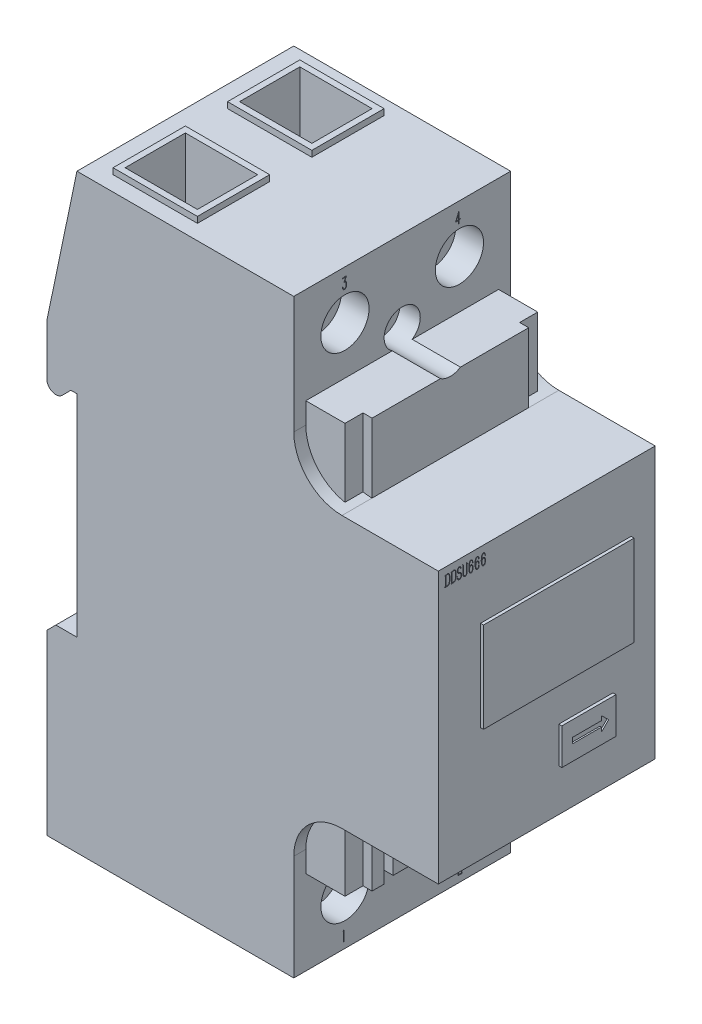
SolidWorks part; units mm, degrees
ref_plane "前视基准面" through (0, 0, 0) normal (0, 0, 1) x (1, 0, 0)
ref_plane "上视基准面" through (0, 0, 0) normal (0, 1, 0) x (1, 0, 0)
ref_plane "右视基准面" through (0, 0, 0) normal (1, 0, 0) x (0, 0, -1)
other "Configuration Table"
sketch "草图1" plane through (0, 0, 0) normal (0, 0, 1) x (1, 0, 0)
  line L0 (-48.1619, 0) -> (82.3002, 0) construction
  line L1 (0, 18) -> (0, -17)
  line L2 (0, -17) -> (-3.5, -17)
  line L3 (-5, -18.5) -> (-5, -48)
  line L4 (-5, -48) -> (36, -48)
  line L5 (36, -48) -> (36, -30.5)
  line L6 (44, -22.5) -> (60, -22.5)
  line L7 (60, -22.5) -> (60, 22.5)
  line L8 (60, 22.5) -> (44, 22.5)
  line L9 (36, 30.5) -> (36, 50)
  line L10 (36, 50) -> (0, 50)
  line L11 (0, 50) -> (-5, 26)
  line L12 (-5, 26) -> (-5, 17.6213)
  line L14 (0, 18) -> (-1, 18)
  line L15 (-1, 18) -> (-2.4393, 16.5607)
  line L16 (-3.5, -17) -> (-5, -18.5)
  arc A0 (36, -30.5) -> (44, -22.5) centre (44, -30.5) cw
  arc A1 (36, 30.5) -> (44, 22.5) centre (44, 30.5) ccw
  arc A2 (-5, 17.6213) -> (-2.4393, 16.5607) centre (-3.5, 17.6213) ccw
  point P5 (-5, -17)
  point P8 (60, 0)
  point P24 (-5, 14)
  dimension "D12" = 8
  dimension "D13" = 1.5
  dimension "D1" = 35
  dimension "D2" = 5
  dimension "D3" = 98
  dimension "D4" = 31
  dimension "D5" = 60
  dimension "D6" = 41
  dimension "D7" = 1
  dimension "D8" = 12
  dimension "D9" = 45
  dimension "D10" = 50
  dimension "D11" = 45
extrude "凸台-拉伸1" add sketch "草图1" along normal mid plane 36
sketch "草图3" plane through (0, 0, 0) normal (0, 1, 0) x (1, 0, 0)
  line L0 (36, -18) -> (36, 18) construction
  line L1 (36, -18) -> (36, 18) construction
  line L2 (24.7811, 0) -> (53.8019, 0) construction
  line L3 (36, 16) -> (36, -16)
  line L4 (36, -16) -> (42.5, -16)
  line L5 (42.5, -16) -> (42.5, -13)
  line L6 (42.5, -13) -> (44, -13)
  line L7 (44, -13) -> (44, 13)
  line L8 (44, 13) -> (42.5, 13)
  line L9 (42.5, 13) -> (42.5, 16)
  line L10 (42.5, 16) -> (36, 16)
  dimension "D1" = 6.5
  dimension "D2" = 8
  dimension "D3" = 32
  dimension "D4" = 26
extrude "凸台-拉伸4" add sketch "草图3" along normal mid plane 68
sketch "草图4" plane through (0, -22.5, 0) normal (0, -1, 0) x (1, 0, 0)
  line L0 (42.8853, 0) -> (54.8516, 0) construction
  line L2 (44, 13) -> (44, -13) construction
  line L4 (44, 13) -> (48, 13)
  line L5 (44, 13) -> (44, -13)
  line L6 (48, 13) -> (48, -13)
  line L7 (48, -13) -> (44, -13)
  dimension "D1" = 4
extrude "凸台-拉伸5" add sketch "草图4" along normal blind 4
sketch "草图5" plane through (0, -34, 0) normal (0, -1, 0) x (1, 0, 0)
  line L0 (48, -13) -> (48, 13) construction
  line L1 (48, -13) -> (48, 13)
  line L2 (28.9933, 0) -> (51.5375, 0) construction
  line L3 (36, 11) -> (36, -11)
  line L4 (36, -16) -> (36, 16) construction
  line L5 (36, -11) -> (46.5, -11)
  line L6 (46.5, -11) -> (46.5, 11)
  line L7 (46.5, 11) -> (36, 11)
  dimension "D1" = 1.5
  dimension "D2" = 22
extrude "切除-拉伸1" cut sketch "草图5" against normal blind 15 contours L3 L5 L6 L7
sketch "草图6" plane through (36, 0, 0) normal (1, 0, 0) x (0, 0, -1)
  line L0 (0, -48.641) -> (0, -19.05) construction
  line L1 (11, -26.5) -> (11, -34) construction
  line L2 (-10.5, -32.5) -> (10.5, -32.5)
  line L3 (-10.5, -32.5) -> (-10.5, -20.5)
  line L4 (-10.5, -20.5) -> (10.5, -20.5)
  line L5 (10.5, -32.5) -> (10.5, -20.5)
  line L6 (-10.5, -32.5) -> (10.5, -20.5) construction
  line L7 (-10.5, -20.5) -> (10.5, -32.5) construction
  line L8 (16, -34) -> (11, -34) construction
  point P3 (0, -26.5)
  dimension "D1" = 0.5
  dimension "D2" = 1.5
  dimension "D3" = 12
extrude "凸台-拉伸6" add sketch "草图6" along normal offset from surface (9 mm away) 1.5 up to face at (46.5, -22.75, 0)
hole_wizard "M2 开槽圆柱头螺钉的柱形沉头孔1" positions "草图15" profile "草图10" counterbore size "M2" standard "GB"
sketch "草图15" plane through (45, 0, 0) normal (1, 0, 0) x (0, 0, -1)
  line L0 (0, 4.0019) -> (0, -34.6889) construction
  line L3 (-10.5, -29.5) -> (10.5, -29.5) construction
  line L4 (-10.5, -20.5) -> (-10.5, -32.5) construction
  line L5 (10.5, -32.5) -> (10.5, -20.5) construction
  line L7 (13, -26.5) -> (-13, -26.5) construction
  point P0 (-7.5, -29.5)
  point P2 (-2.5, -29.5)
  point P4 (2.5, -29.5)
  point P6 (7.5, -29.5)
  dimension "D1" = 5
  dimension "D2" = 5
  dimension "D3" = 3
sketch "草图10" plane through (45, -29.5, 7.5) normal (0, 1, 0) x (0, 0, -1)
  line L0 (0, 0) -> (0, 4.721)
  line L1 (0, 4.721) -> (1.2, 4)
  line L2 (1.2, 4) -> (1.2, 2.3)
  line L3 (1.2, 2.3) -> (2.15, 2.3)
  line L4 (2.15, 2.3) -> (2.15, 0)
  line L5 (2.15, 0) -> (0, 0)
  line L10 (0, 4.721) -> (-1.2, 4) construction
  line L11 (0, -6.35) -> (0, 107.95) construction
  dimension "孔直径" = 2.4
  dimension "孔深度" = 4
  dimension "柱形沉头孔直径" = 4.3
  dimension "柱形沉头孔深度" = 2.3
  dimension "导头角度" = 118
sketch "草图16" plane through (0, -32.5, 0) normal (0, -1, 0) x (1, 0, 0)
  line L0 (40.5, 10.5) -> (40.5, -10.5) construction
  line L1 (45, 10.5) -> (36, 10.5) construction
  line L2 (45, -10.5) -> (36, -10.5) construction
  line L3 (36.8244, 0) -> (43.3826, 0) construction
  line L5 (42.25, 4.25) -> (38.75, 4.25)
  line L6 (42.25, 4.25) -> (42.25, 0.75)
  line L7 (42.25, 0.75) -> (38.75, 0.75)
  line L8 (38.75, 4.25) -> (38.75, 0.75)
  line L9 (42.25, 4.25) -> (38.75, 0.75) construction
  line L10 (42.25, 0.75) -> (38.75, 4.25) construction
  line L12 (38.75, -4.25) -> (38.75, -0.75)
  line L13 (42.25, -0.75) -> (38.75, -0.75)
  line L14 (42.25, -4.25) -> (42.25, -0.75)
  line L15 (42.25, -4.25) -> (38.75, -4.25)
  line L16 (38.75, -5.75) -> (42.25, -5.75)
  line L17 (38.75, 9.25) -> (42.25, 9.25)
  line L18 (38.75, 9.25) -> (38.75, 5.75)
  line L19 (38.75, 5.75) -> (42.25, 5.75)
  line L20 (42.25, 9.25) -> (42.25, 5.75)
  line L21 (38.75, 9.25) -> (42.25, 5.75) construction
  line L22 (38.75, 5.75) -> (42.25, 9.25) construction
  line L23 (38.75, -9.25) -> (38.75, -5.75)
  line L24 (38.75, -9.25) -> (42.25, -9.25)
  line L25 (42.25, -9.25) -> (42.25, -5.75)
  point P9 (40.5, 2.5)
  point P19 (38.75, 2.5)
  point P20 (38.75, -2.5)
  point P21 (40.5, 7.5)
  point P29 (38.75, 7.5)
  dimension "D1" = 3.5
  dimension "D2" = 5
  dimension "D3" = 5
extrude "切除-拉伸2" cut sketch "草图16" against normal blind 2
hole_wizard "M4 开槽圆柱头螺钉的柱形沉头孔1" positions "草图20" profile "草图19" counterbore size "M4" standard "GB"
sketch "草图20" plane through (36, 0, 0) normal (1, 0, 0) x (0, 0, -1)
  line L0 (-16.3132, 42) -> (15.3429, 42) construction
  line L2 (-18, 50) -> (18, 50) construction
  line L3 (0, 35.6579) -> (0, 47.3622) construction
  line L4 (-22.9234, 0) -> (24.0756, 0) construction
  line L6 (-16.3132, -40) -> (15.3429, -40) construction
  line L8 (0, -45.3622) -> (0, -34.8102) construction
  line L10 (-18, -48) -> (18, -48) construction
  point P0 (-9.5, 42)
  point P2 (9.5, 42)
  point P19 (-9.5, -40)
  point P21 (9.5, -40)
  dimension "D1" = 8
  dimension "D2" = 19
  dimension "D3" = 8
sketch "草图19" plane through (36, 42, 9.5) normal (0, 1, 0) x (0, 0, -1)
  line L0 (0, 0) -> (0, 6.3519)
  line L1 (0, 6.3519) -> (2.25, 5)
  line L2 (2.25, 5) -> (2.25, 4.6)
  line L3 (2.25, 4.6) -> (4, 4.6)
  line L4 (4, 4.6) -> (4, 0)
  line L5 (4, 0) -> (0, 0)
  line L10 (0, 6.3519) -> (-2.25, 5) construction
  line L11 (0, -6.35) -> (0, 107.95) construction
  dimension "孔直径" = 4.5
  dimension "孔深度" = 5
  dimension "柱形沉头孔直径" = 8
  dimension "柱形沉头孔深度" = 4.6
  dimension "导头角度" = 118
hole_wizard "M3 开槽圆柱头螺钉的柱形沉头孔1" positions "草图21" profile "草图22" counterbore size "M3" standard "GB"
sketch "草图21" plane through (36, 0, 0) normal (1, 0, 0) x (0, 0, -1)
  line L0 (-10.5, -32.5) -> (10.5, -32.5) construction
  line L1 (16, 34) -> (-16, 34) construction
  point P0 (0, 36.5)
  point P2 (0, -36.5)
  dimension "D1" = 4
  dimension "D2" = 2.5
sketch "草图22" plane through (36, 36.5, 0) normal (0, 1, 0) x (0, 0, -1)
  line L0 (0, 0) -> (0, 6.0215)
  line L1 (0, 6.0215) -> (1.7, 5)
  line L2 (1.7, 5) -> (1.7, 3.4)
  line L3 (1.7, 3.4) -> (3, 3.4)
  line L4 (3, 3.4) -> (3, 0)
  line L5 (3, 0) -> (0, 0)
  line L10 (0, 6.0215) -> (-1.7, 5) construction
  line L11 (0, -6.35) -> (0, 107.95) construction
  dimension "孔直径" = 3.4
  dimension "孔深度" = 5
  dimension "柱形沉头孔直径" = 6
  dimension "柱形沉头孔深度" = 3.4
  dimension "导头角度" = 118
sketch "草图23" plane through (44, 0, 0) normal (1, 0, 0) x (0, 0, -1)
  arc A0 (1.6583, 34) -> (-1.6583, 34) centre (0, 36.5) ccw construction
  arc A1 (1.6583, 34) -> (-1.6583, 34) centre (0, 36.5) ccw
  circle A2 centre (0, 36.5) radius 3
extrude "切除-拉伸3" cut sketch "草图23" against normal up to surface (8 mm away) contours A2 up to face at (36, 42, 5.5)
sketch "草图24" plane through (0, -48, 0) normal (0, -1, 0) x (1, 0, 0)
  line L0 (-12.0044, 0) -> (32.1311, 0) construction
  line L1 (10.5, 14.5663) -> (10.5, -16.6083) construction
  line L2 (3, -6) -> (-3, -6)
  line L3 (3, -6) -> (3, 6)
  line L4 (3, 6) -> (-3, 6)
  line L5 (-3, -6) -> (-3, 6)
  line L6 (3, -6) -> (-3, 6) construction
  line L7 (3, 6) -> (-3, -6) construction
  line L8 (-5, 18) -> (-5, -18) construction
  line L9 (-5, 18) -> (36, 18) construction
  line L10 (17.5, 15.5) -> (3.5, 15.5)
  line L11 (17.5, 15.5) -> (17.5, 3.5)
  line L12 (17.5, 3.5) -> (3.5, 3.5)
  line L13 (3.5, 15.5) -> (3.5, 3.5)
  line L14 (17.5, 15.5) -> (3.5, 3.5) construction
  line L15 (17.5, 3.5) -> (3.5, 15.5) construction
  line L16 (3.5, -15.5) -> (3.5, -3.5)
  line L17 (17.5, -3.5) -> (3.5, -3.5)
  line L18 (17.5, -15.5) -> (17.5, -3.5)
  line L19 (17.5, -15.5) -> (3.5, -15.5)
  line L20 (16.5, 14.5) -> (4.5, 14.5)
  line L21 (4.5, 14.5) -> (4.5, 4.5)
  line L22 (16.5, 4.5) -> (4.5, 4.5)
  line L23 (16.5, 14.5) -> (16.5, 4.5)
  line L24 (16.5, -4.5) -> (4.5, -4.5)
  line L25 (4.5, -14.5) -> (4.5, -4.5)
  line L26 (16.5, -14.5) -> (4.5, -14.5)
  line L27 (16.5, -14.5) -> (16.5, -4.5)
  point P3 (0, 0)
  point P13 (10.5, 9.5)
  dimension "D1" = 2
  dimension "D2" = 12
  dimension "D3" = 6
  dimension "D4" = 0.5
  dimension "D5" = 14
  dimension "D6" = 12
  dimension "D7" = 2.5
  dimension "D8" = 1
extrude "凸台-拉伸7" add sketch "草图24" along normal blind 1 contours L10 L13 L12 L11 | L17 L16 L19 L18
extrude "切除-拉伸4" cut sketch "草图24<4>" against normal blind 10 and the other way through all contours L20 L21 L22 L23 | L24 L25 L26 L27
sketch "草图24<4>" plane through (0, -48, 0) normal (0, -1, 0) x (1, 0, 0) same geometry as "草图24"
extrude "切除-拉伸5" cut sketch "草图24<5>" against normal up to surface (31 mm away) contours L4 L5 L2 L3 up to face at (-1.75, -17, 0)
sketch "草图24<5>" plane through (0, -48, 0) normal (0, -1, 0) x (1, 0, 0) same geometry as "草图24"
sketch "草图27" plane through (0, 50, 0) normal (0, 1, 0) x (1, 0, 0)
  line L0 (17.5, -15.5) -> (3.5, -15.5) construction
  line L1 (17.5, -15.5) -> (17.5, -3.5) construction
  line L2 (3.5, -15.5) -> (3.5, -3.5) construction
  line L3 (17.5, -3.5) -> (3.5, -3.5) construction
  line L4 (3.5, 15.5) -> (3.5, 3.5) construction
  line L5 (17.5, 15.5) -> (3.5, 15.5) construction
  line L6 (17.5, 15.5) -> (17.5, 3.5) construction
  line L7 (17.5, 3.5) -> (3.5, 3.5) construction
  line L8 (17.5, -15.5) -> (3.5, -15.5)
  line L9 (17.5, -15.5) -> (17.5, -3.5)
  line L10 (3.5, -15.5) -> (3.5, -3.5)
  line L11 (17.5, -3.5) -> (3.5, -3.5)
  line L12 (3.5, 15.5) -> (3.5, 3.5)
  line L13 (17.5, 15.5) -> (3.5, 15.5)
  line L14 (17.5, 15.5) -> (17.5, 3.5)
  line L15 (17.5, 3.5) -> (3.5, 3.5)
  line L16 (16.5, 14.5) -> (4.5, 14.5)
  line L17 (4.5, 14.5) -> (4.5, 4.5)
  line L18 (16.5, 4.5) -> (4.5, 4.5)
  line L19 (16.5, 14.5) -> (16.5, 4.5)
  line L20 (16.5, -4.5) -> (4.5, -4.5)
  line L21 (4.5, -14.5) -> (4.5, -4.5)
  line L22 (16.5, -14.5) -> (4.5, -14.5)
  line L23 (16.5, -14.5) -> (16.5, -4.5)
  dimension "D1" = 1
extrude "凸台-拉伸8" add sketch "草图27" along normal blind 1 contours L13 L12 L15 L14 | L11 L10 L8 L9
extrude "切除-拉伸6" cut sketch "草图27<3>" against normal blind 10 and the other way through all contours L17 L18 L19 L16 | L20 L21 L22 L23
sketch "草图27<3>" plane through (0, 50, 0) normal (0, 1, 0) x (1, 0, 0) same geometry as "草图27"
sketch "文字1" plane through (36, 0, 0) normal (1, 0, 0) x (0, 0, -1)
  text T0 "1" font "汉仪长仿宋体" height 2
extrude "切除-拉伸7" cut sketch "文字1" against normal blind 0.25
sketch "文字2" plane through (36, 0, 0) normal (1, 0, 0) x (0, 0, -1)
  text T0 "2" font "汉仪长仿宋体" height 2
extrude "切除-拉伸8" cut sketch "文字2" against normal blind 0.25
sketch "文字3" plane through (36, 0, 0) normal (1, 0, 0) x (0, 0, -1)
  text T0 "3" font "汉仪长仿宋体" height 2
extrude "切除-拉伸9" cut sketch "文字3" against normal blind 0.25
sketch "文字4" plane through (36, 0, 0) normal (1, 0, 0) x (0, 0, -1)
  text T0 "4" font "汉仪长仿宋体" height 2
extrude "切除-拉伸10" cut sketch "文字4" against normal blind 0.25
sketch "文字562425" plane through (36, 0, 0) normal (1, 0, 0) x (0, 0, -1)
  text T0 "5  6        24  25" font "汉仪长仿宋体" height 2
extrude "切除-拉伸11" cut sketch "文字562425" against normal blind 0.25
sketch "草图34" plane through (60, 0, 0) normal (1, 0, 0) x (0, 0, -1)
  line L0 (18, -22.5) -> (18, 22.5) construction
  line L1 (14, -3.5) -> (-11, -3.5)
  line L2 (14, -3.5) -> (14, 11.5)
  line L3 (14, 11.5) -> (-11, 11.5)
  line L4 (-11, -3.5) -> (-11, 11.5)
  line L5 (14, -3.5) -> (-11, 11.5) construction
  line L6 (14, 11.5) -> (-11, -3.5) construction
  line L7 (2, -9.5) -> (11, -9.5)
  line L8 (2, -9.5) -> (2, -15.5)
  line L9 (2, -15.5) -> (11, -15.5)
  line L10 (11, -9.5) -> (11, -15.5)
  line L11 (2, -9.5) -> (11, -15.5) construction
  line L12 (2, -15.5) -> (11, -9.5) construction
  line L13 (13, 22.5) -> (18, 22.5) construction
  line L14 (-18, -22.5) -> (18, -22.5) construction
  point P0 (1.5, 4)
  point P5 (6.5, -12.5)
  dimension "D1" = 25
  dimension "D2" = 15
  dimension "D3" = 6
  dimension "D4" = 9
  dimension "D5" = 7
  dimension "D6" = 4
  dimension "D7" = 11
  dimension "D8" = 7
extrude "凸台-拉伸9" add sketch "草图34" along normal blind 0.5
sketch "文字DDSU666" plane through (60, 0, 0) normal (1, 0, 0) x (0, 0, -1)
  text T0 "DDSU666" font "汉仪长仿宋体" height 2
extrude "切除-拉伸12" cut sketch "文字DDSU666" against normal blind 0.25
sketch "草图36" plane through (60.5, 0, 0) normal (1, 0, 0) x (0, 0, -1)
  line L0 (2, -12.5) -> (11, -12.5) construction
  line L1 (2, -9.5) -> (2, -15.5) construction
  line L2 (11, -15.5) -> (11, -9.5) construction
  line L3 (3.8124, -12.0385) -> (3.8124, -12.9615)
  line L4 (3.8124, -12.9615) -> (8.5829, -12.9615)
  line L5 (8.5829, -12.9615) -> (8.5829, -13.6821)
  line L6 (8.5829, -13.6821) -> (9.765, -12.5)
  line L7 (9.765, -12.5) -> (8.5829, -11.3179)
  line L8 (8.5829, -11.3179) -> (8.5829, -12.0385)
  line L9 (8.5829, -12.0385) -> (3.8124, -12.0385)
extrude "切除-拉伸13" cut sketch "草图36" against normal blind 0.25
